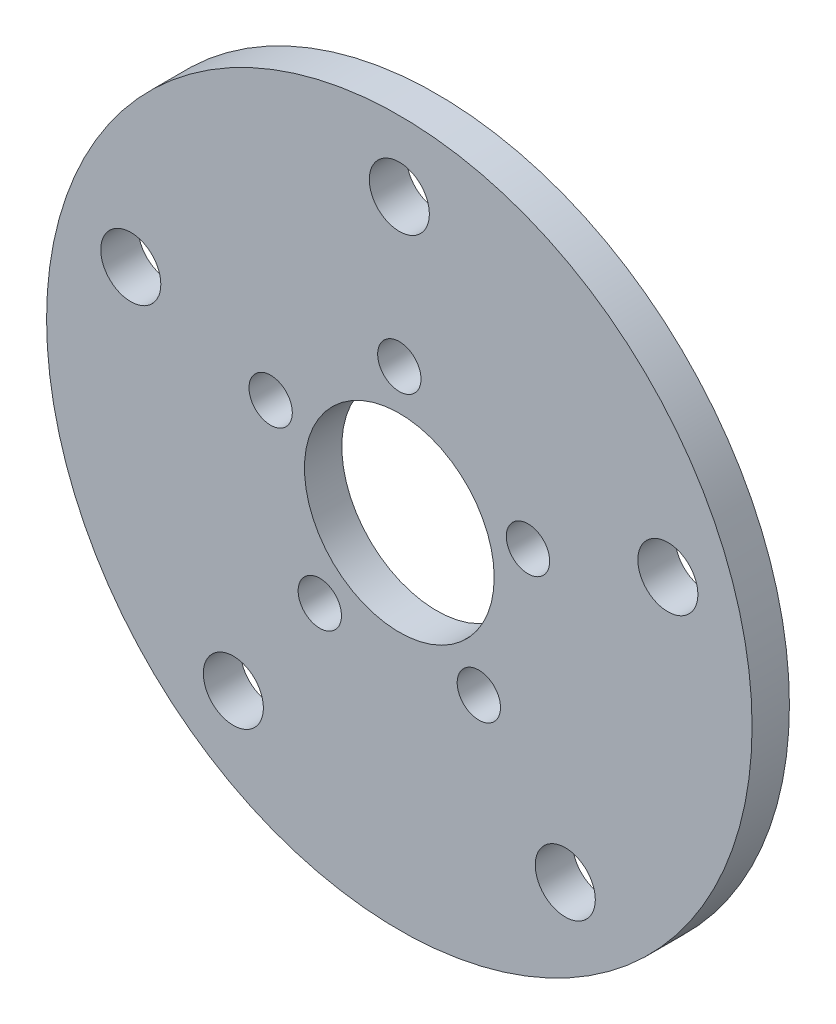
SolidWorks part; units mm, degrees
ref_plane "Front Plane" through (0, 0, 0) normal (0, 0, 1) x (1, 0, 0)
ref_plane "Top Plane" through (0, 0, 0) normal (0, 1, 0) x (1, 0, 0)
ref_plane "Right Plane" through (0, 0, 0) normal (1, 0, 0) x (0, 0, -1)
sketch "Sketch1" plane through (0, 0, 0) normal (0, 0, 1) x (1, 0, 0)
  line L0 (0, 0) -> (0, 11.5) construction
  line L1 (0, 24) -> (0, 0) construction
  circle A0 centre (0, 0) radius 29.9847
  circle A1 centre (0, 0) radius 8.0645
  circle A2 centre (0, 11.5) radius 1.8415
  circle A3 centre (0, 24) radius 2.5527
  circle A4 centre (10.9371, 3.5537) radius 1.8415
  circle A5 centre (22.8254, 7.4164) radius 2.5527
  circle A6 centre (6.7595, -9.3037) radius 1.8415
  circle A7 centre (14.1068, -19.4164) radius 2.5527
  circle A8 centre (-6.7595, -9.3037) radius 1.8415
  circle A9 centre (-14.1068, -19.4164) radius 2.5527
  circle A10 centre (-10.9371, 3.5537) radius 1.8415
  circle A11 centre (-22.8254, 7.4164) radius 2.5527
  circle A12 centre (0, 0) radius 29.9847 construction
  dimension "D2" = 16.129
  dimension "D4" = 3.683
  dimension "D5" = 5.1054
  dimension "D3" = 11.5
  dimension "D6" = 24
  dimension "D7" = 5
extrude "Boss-Extrude1" add sketch "Sketch1" along normal blind 3.175
